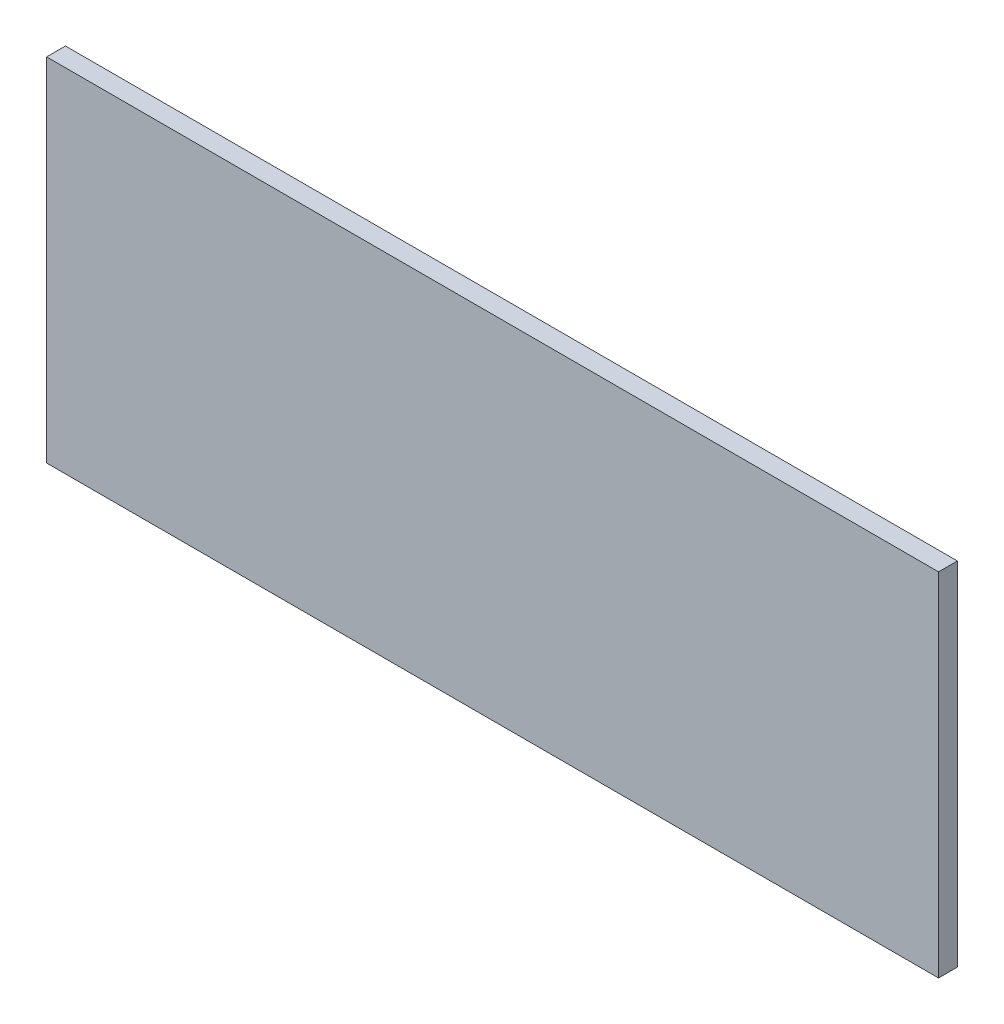
SolidWorks part; units mm, degrees
material "PEI"
ref_plane "Front Plane" through (0, 0, 0) normal (0, 0, 1) x (1, 0, 0)
ref_plane "Top Plane" through (0, 0, 0) normal (0, 1, 0) x (1, 0, 0)
ref_plane "Right Plane" through (0, 0, 0) normal (1, 0, 0) x (0, 0, -1)
sketch "Sketch2" plane through (0, 0, 0) normal (0, 0, 1) x (1, 0, 0)
  line L1 (56, -28) -> (-56, -28)
  line L2 (56, -28) -> (56, 28)
  line L3 (56, 28) -> (-56, 28)
  line L4 (-56, -28) -> (-56, 28)
  line L5 (56, -28) -> (-56, 28) construction
  line L6 (56, 28) -> (-56, -28) construction
  line L7 (56, 28) -> (86, 28)
  line L8 (56, 28) -> (56, -28)
  line L9 (56, -28) -> (86, -28)
  line L10 (86, 28) -> (86, -28)
  point P0 (0, 0)
  dimension "D1" = 112
  dimension "D2" = 56
  dimension "D3" = 30
extrude "Boss-Extrude1" add sketch "Sketch2" along normal blind 3 contours L4 L1 L2 L3 | L10 L7 L2 L9 region at (0, 0, 0) region at (71, 0, 0)
